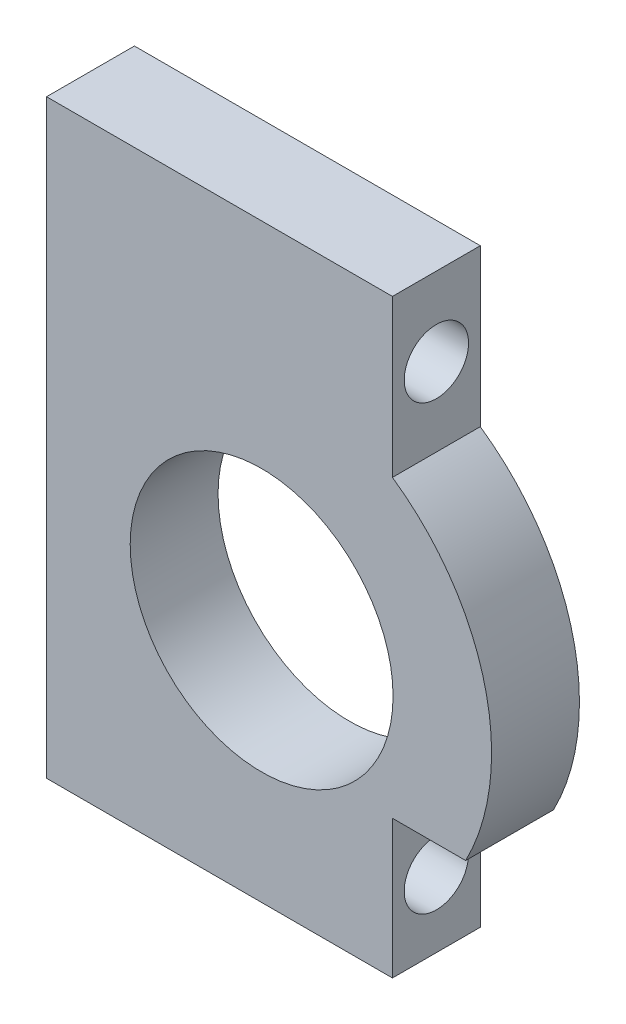
SolidWorks part; units mm, degrees
material "1060 Alloy"
ref_plane "Front Plane" through (0, 0, 0) normal (0, 0, 1) x (1, 0, 0)
ref_plane "Top Plane" through (0, 0, 0) normal (0, 1, 0) x (1, 0, 0)
ref_plane "Right Plane" through (0, 0, 0) normal (1, 0, 0) x (0, 0, -1)
sketch "Sketch2" plane through (0, 0, -13.2) normal (0, 0, -1) x (-1, 0, 0)
  line L0 (-19.1, 36.72) -> (-44.1, 36.72) construction
  line L1 (-44.1, 36.72) -> (-44.1, 46.72) construction
  line L2 (-19.1, 36.72) -> (-19.1, 79.385) construction
  line L3 (-19.1, 79.385) -> (-44.1, 79.385) construction
  line L4 (-44.1, 79.385) -> (-44.1, 68.055) construction
  line L5 (-44.1, 46.72) -> (-49.3933, 46.72) construction
  line L6 (-19.1, 36.72) -> (-44.1, 36.72)
  line L7 (-44.1, 36.72) -> (-44.1, 46.72)
  line L8 (-19.1, 36.72) -> (-19.1, 79.385)
  line L9 (-19.1, 79.385) -> (-44.1, 79.385)
  line L10 (-44.1, 79.385) -> (-44.1, 68.055)
  line L11 (-44.1, 46.72) -> (-49.3933, 46.72)
  arc A0 (-44.1, 68.055) -> (-49.3933, 46.72) centre (-34.645, 54.385) ccw construction
  arc A1 (-44.1, 68.055) -> (-49.3933, 46.72) centre (-34.645, 54.385) ccw
  circle A2 centre (-34.645, 54.385) radius 9.5
  circle A3 centre (-34.645, 54.385) radius 9.5 construction
  circle A4 centre (-34.645, 54.385) radius 5 construction
  circle A5 centre (-34.645, 54.385) radius 5 construction
extrude "Boss-Extrude1" add sketch "Sketch2" along normal blind 3.175 and the other way blind 3.175
sketch "Sketch3" plane through (44.1, 0, 0) normal (1, 0, 0) x (0, 0, -1)
  line L0 (13.2, 41.72) -> (0, 41.72) construction
  line L1 (13.2, 41.72) -> (13.2, 73.72) construction
  line L2 (16.375, 46.72) -> (16.375, 36.72) construction
  line L3 (10.025, 46.72) -> (10.025, 36.72) construction
  line L4 (0, 39.395) -> (13.2, 39.395) construction
  line L5 (13.2, 73.72) -> (0, 73.72) construction
  circle A0 centre (13.2, 41.72) radius 2.325
  circle A1 centre (13.2, 73.72) radius 2.325
extrude "Cut-Extrude1" cut sketch "Sketch3" against normal up to next
